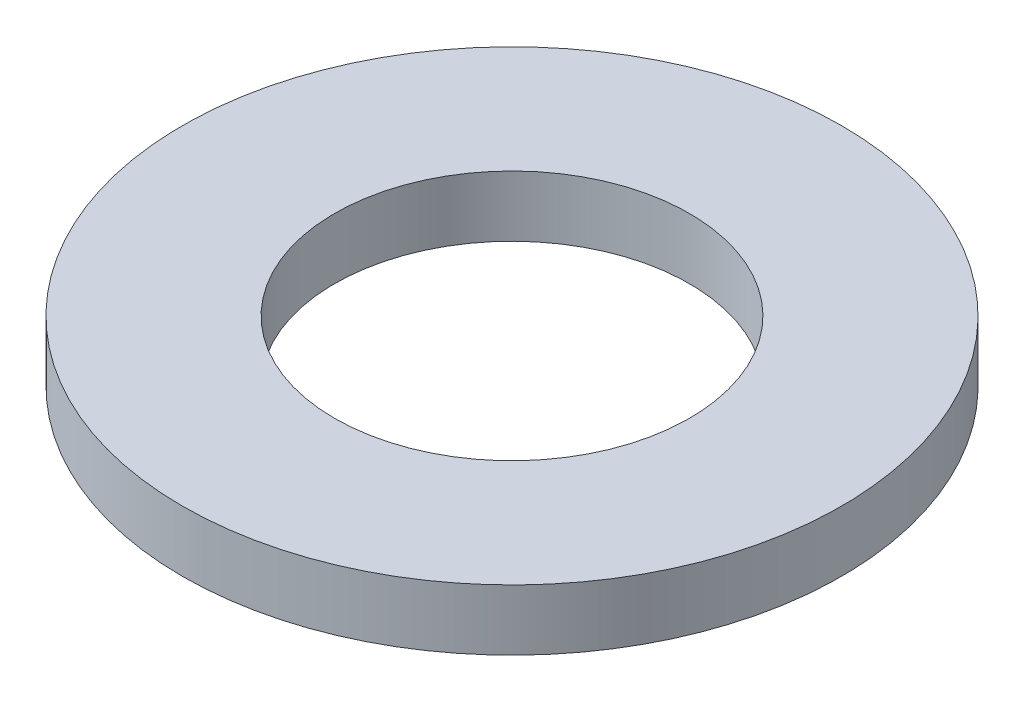
SolidWorks part; units mm, degrees
ref_plane "Front Plane" through (0, 0, 0) normal (0, 0, 1) x (1, 0, 0)
ref_plane "Top Plane" through (0, 0, 0) normal (0, 1, 0) x (1, 0, 0)
ref_plane "Right Plane" through (0, 0, 0) normal (1, 0, 0) x (0, 0, -1)
sketch "Sketch1" plane through (0, 0, 0) normal (0, 1, 0) x (1, 0, 0)
  circle A0 centre (0, 0) radius 65
  dimension "FLANGE_OD" = 130
extrude "Boss-Extrude1" add sketch "Sketch1" along normal blind 12
sketch "Sketch2" plane through (0, 0, 0) normal (0, 1, 0) x (1, 0, 0)
  circle A0 centre (0, 0) radius 35
  dimension "BORE_D" = 70
extrude "Cut-Extrude1" cut sketch "Sketch2" along normal through all
sketch "Sketch3" plane through (0, 12, 0) normal (0, 1, 0) x (1, 0, 0)
  circle A0 centre (0, 0) radius 28.4027 construction
  circle A1 centre (-28.4027, 0) radius 3.2933
  dimension "BOLT_D" = 6.5867
  dimension "BOLT_PCD" = 56.8054
extrude "Cut-Extrude2" cut sketch "Sketch3" against normal blind 11.3265 rebuild error yes
pattern_circular "CirPattern1" count 5 over 360 rebuild error yes
